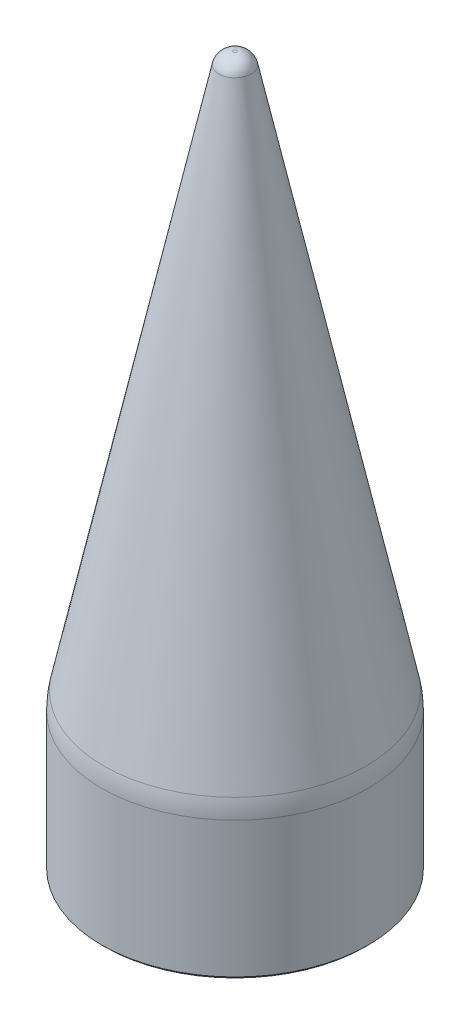
SolidWorks part; units mm, degrees
ref_plane "前视基准面" through (0, 0, 0) normal (0, 0, 1) x (1, 0, 0)
ref_plane "上视基准面" through (0, 0, 0) normal (0, 1, 0) x (1, 0, 0)
ref_plane "右视基准面" through (0, 0, 0) normal (1, 0, 0) x (0, 0, -1)
other "Configuration Table"
sketch "草图1" plane through (0, 0, 0) normal (0, 1, 0) x (1, 0, 0)
  circle A0 centre (0, 0) radius 45
  dimension "D1" = 90
extrude "凸台-拉伸1" add sketch "草图1" along normal blind 50
sketch "草图2" plane through (0, 0, 0) normal (0, -1, 0) x (-1, 0, 0)
  circle A0 centre (0, 0) radius 37.5
  dimension "D1" = 75
extrude "切除-拉伸1" cut sketch "草图2" against normal blind 50
ref_plane "基准面1" through (0, 0, 40) normal (0, 0, 1) x (1, 0, 0)
sketch "草图3" plane through (0, 0, 40) normal (0, 0, 1) x (1, 0, 0)
  circle A0 centre (0, 36.8514) radius 7.5
  dimension "D1" = 15
extrude "凸台-拉伸2" add sketch "草图3" against normal blind 80
sketch "草图4" plane through (0, 50, 0) normal (0, 1, 0) x (1, 0, 0)
  circle A0 centre (0, 0) radius 45
  dimension "D1" = 90
extrude "凸台-拉伸3" add sketch "草图4" along normal blind 190 draft 12
fillet "圆角1" radius 5 1 edges at (0, 240, 4.6143)
fillet "圆角2" radius 30 1 edges at (0, 50, 45)
chamfer "倒角1" distance 1 angle 45 2 edges at (0, 0, 45) (0, 0, -37.5)
